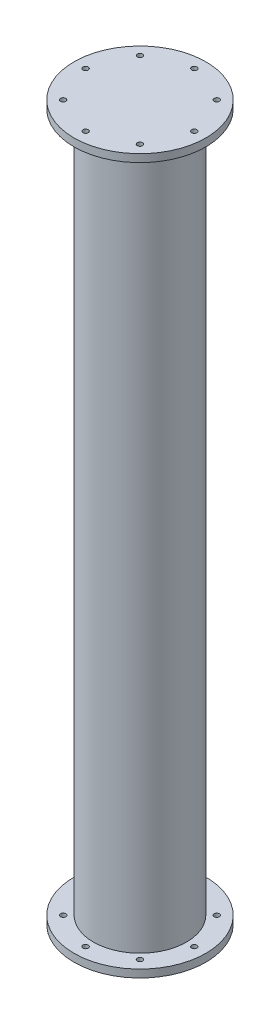
SolidWorks part; units mm, degrees
material "6063-T5"
ref_plane "Front" through (0, 0, 0) normal (0, 0, 1) x (1, 0, 0)
ref_plane "Top" through (0, 0, 0) normal (0, 1, 0) x (1, 0, 0)
ref_plane "Right" through (0, 0, 0) normal (1, 0, 0) x (0, 0, -1)
sketch "Croquis1" plane through (0, 0, 0) normal (0, 1, 0) x (1, 0, 0)
  circle A0 centre (0, 0) radius 30
  circle A1 centre (0, 0) radius 25
  dimension "DE" = 60
  dimension "DI" = 50
extrude "Saliente-Extruir1" add sketch "Croquis1" along normal mid plane 450
sketch "Croquis2" plane through (0, 225, 0) normal (0, 1, 0) x (1, 0, 0)
  line L0 (0, 42.5) -> (0, 32.7) construction
  circle A0 centre (0, 0) radius 42.5
  dimension "D1" = 85
extrude "Saliente-Extruir2" add sketch "Croquis2" along normal blind 5
hole_wizard "Taladro de margen para M31" positions "Croquis3" profile "Croquis4" hole size "M3" standard "Ansi Metric" end condition up to next
sketch "Croquis3" plane through (0, 225, 0) normal (0, -1, 0) x (-1, 0, 0)
  line L3 (0, 46.75) -> (0, -46.75) construction
  circle A0 centre (0, 0) radius 35 construction
  point P13 (-24.7487, -24.7487)
  point P21 (-35, 0)
  point P22 (-24.7487, 24.7487)
  point P23 (0, 35)
  point P24 (24.7487, 24.7487)
  point P25 (35, 0)
  point P34 (24.7487, -24.7487)
  point P35 (0, -35)
  dimension "D1" = 70
  dimension "D2" = 8
sketch "Croquis4" plane through (0, 225, 35) normal (1, 0, 0) x (0, 0, -1)
  line L0 (0, 0) -> (0, 5.001)
  line L1 (0, 5.001) -> (1.7, 5.001)
  line L2 (1.7, 5.001) -> (1.7, 0)
  line L5 (1.7, 0) -> (0, 0)
  line L11 (0, -6.35) -> (0, 107.95) construction
  dimension "Diámetro de taladro hasta el siguiente" = 3.4
  dimension "Profundidad de taladro hasta el siguiente" = 5.001
mirror "Simetría1" about plane through (0, 0, 0) normal (0, 1, 0) of "Taladro de margen para M31", "Saliente-Extruir2"
